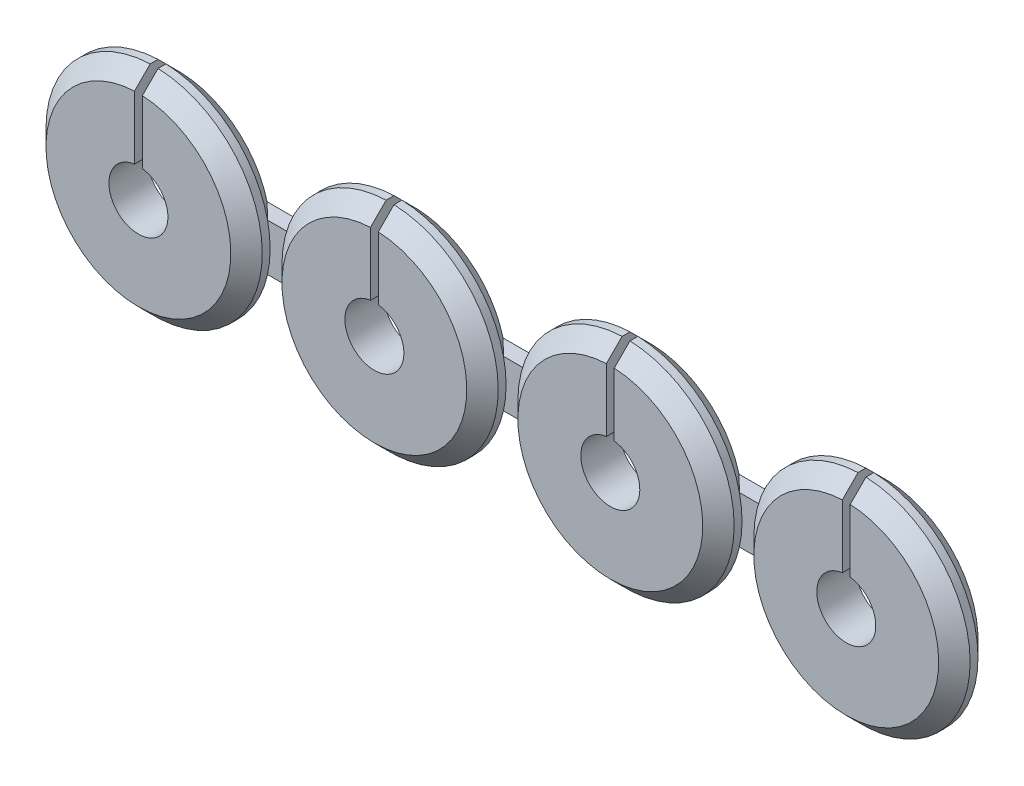
SolidWorks part; units mm, degrees
ref_plane "Front Plane" through (0, 0, 0) normal (0, 0, 1) x (1, 0, 0)
ref_plane "Top Plane" through (0, 0, 0) normal (0, 1, 0) x (1, 0, 0)
ref_plane "Right Plane" through (0, 0, 0) normal (1, 0, 0) x (0, 0, -1)
sketch "Sketch1" plane through (0, 0, 0) normal (0, 0, 1) x (1, 0, 0)
  circle A0 centre (0, 0) radius 1.5
  circle A1 centre (0, 0) radius 5.5
  dimension "D1" = 3
  dimension "D2" = 4
extrude "Boss-Extrude1" add sketch "Sketch1" along normal blind 2
sketch "Sketch2" plane through (0, 0, 2) normal (0, 0, 1) x (1, 0, 0)
  line L1 (-0.2, 5.5) -> (0.2, 5.5)
  line L2 (-0.2, 5.5) -> (-0.2, 1.4866)
  line L3 (-0.2, 1.4866) -> (0.2, 1.4866)
  line L4 (0.2, 5.5) -> (0.2, 1.4866)
  line L5 (0, 1.4866) -> (0, 5.5) construction
  line L6 (-0.2, 3.4933) -> (0.2, 3.4933) construction
  circle A0 centre (0, 0) radius 1.5 construction
  circle A1 centre (0, 0) radius 5.5 construction
  point P0 (0, 3.4933)
  point P6 (0, 0)
  point P9 (0, 0)
  dimension "D1" = 0.4
extrude "Cut-Extrude1" cut sketch "Sketch2" against normal through all
ref_axis "Axis1" through (-6.05, 0, 0) along (1, 0, 0)
chamfer "Chamfer1" distance 0.8 angle 45 2 edges at (0, -5.5, 0) (0, -5.5, 2)
pattern_linear "LPattern1" count 4 spacing 12 along (1, 0, 0) of bodies 102
sketch "Sketch3" plane through (0, 0, 0) normal (0, 0, -1) x (-1, 0, 0)
  line L0 (-19.4558, -1.2) -> (-19.4558, 1.2)
  line L1 (-7.4558, -1.2) -> (-4.5442, -1.2)
  line L2 (-7.4558, -1.2) -> (-7.4558, 1.2)
  line L3 (-7.4558, 1.2) -> (-4.5442, 1.2)
  line L4 (-4.5442, -1.2) -> (-4.5442, 1.2)
  line L5 (-6, 1.2) -> (-6, -1.2) construction
  line L6 (-7.4558, 0) -> (-4.5442, 0) construction
  line L7 (-19.4558, -1.2) -> (-16.5442, -1.2)
  line L8 (-16.5442, -1.2) -> (-16.5442, 1.2)
  line L9 (-19.4558, 1.2) -> (-16.5442, 1.2)
  line L10 (-31.4558, -1.2) -> (-31.4558, 1.2)
  line L11 (-31.4558, -1.2) -> (-28.5442, -1.2)
  line L12 (-28.5442, -1.2) -> (-28.5442, 1.2)
  line L13 (-31.4558, 1.2) -> (-28.5442, 1.2)
  arc A0 (-0.2, 4.6957) -> (0.2, 4.6957) centre (0, 0) ccw construction
  arc A1 (-12.2, 4.6957) -> (-11.8, 4.6957) centre (-12, 0) ccw construction
  arc A2 (-36.2, 4.6957) -> (-35.8, 4.6957) centre (-36, 0) ccw construction
  point P0 (-6, 0)
  point P14 (0, 0)
  dimension "D1" = 2.4
  dimension "D2" = 3
extrude "Boss-Extrude2" add sketch "Sketch3" against normal blind 0.8
